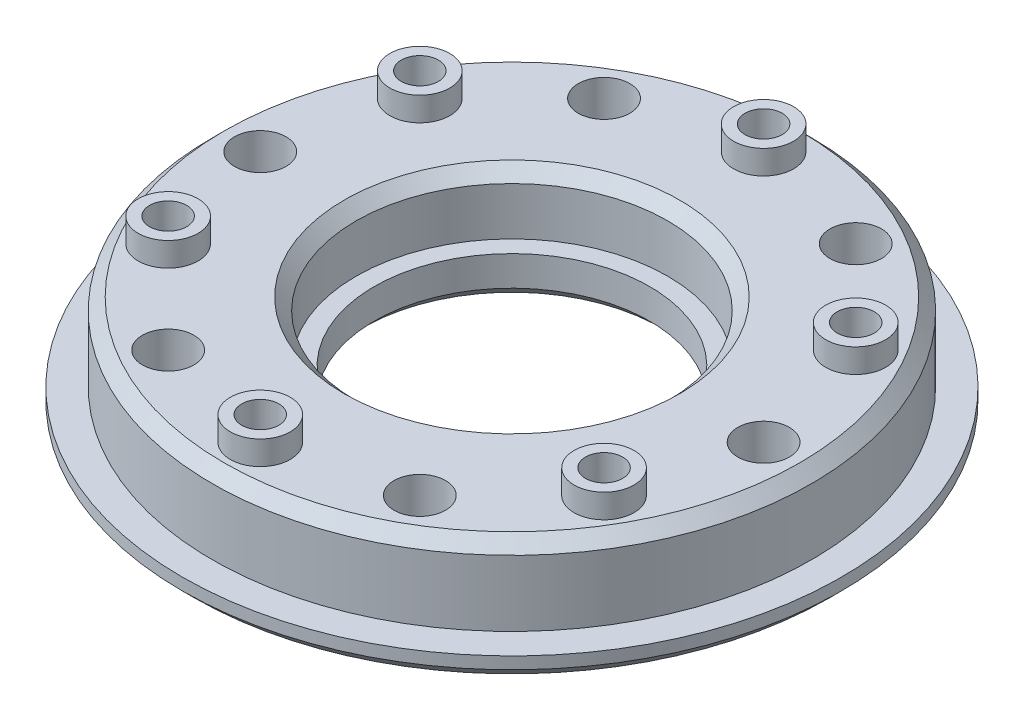
SolidWorks part; units mm, degrees
material "Like ABS"
ref_plane "Front Plane" through (0, 0, 0) normal (0, 0, 1) x (1, 0, 0)
ref_plane "Top Plane" through (0, 0, 0) normal (0, 1, 0) x (1, 0, 0)
ref_plane "Right Plane" through (0, 0, 0) normal (1, 0, 0) x (0, 0, -1)
sketch "Sketch1" plane through (0, 0, 0) normal (0, 1, 0) x (1, 0, 0)
  circle A0 centre (0, 0) radius 27.5
  dimension "D1" = 55
extrude "Boss-Extrude1" add sketch "Sketch1" along normal blind 2
sketch "Sketch2" plane through (0, 2, 0) normal (0, 1, 0) x (1, 0, 0)
  circle A0 centre (0, 0) radius 25
  dimension "D1" = 50
extrude "Boss-Extrude2" add sketch "Sketch2" along normal blind 6.5
sketch "Sketch3" plane through (0, 8.5, 0) normal (0, 1, 0) x (1, 0, 0)
  circle A0 centre (0, 0) radius 13
  dimension "D1" = 26
extrude "Cut-Extrude1" cut sketch "Sketch3" against normal blind 5
sketch "Sketch4" plane through (0, 8.5, 0) normal (0, 1, 0) x (1, 0, 0)
  circle A0 centre (0, 0) radius 11.5
  dimension "D1" = 23
extrude "Cut-Extrude2" cut sketch "Sketch4" against normal up to surface (8.5 mm away) up to face at (0, 0, 27.5)
chamfer "Chamfer1" distance 1 angle 45 4 edges at (0, 0, 27.5) (0, 0, 11.5) (0, 8.5, 13) (0, 8.5, 25)
sketch "Sketch5" plane through (0, 0, 0) normal (0, -1, 0) x (1, 0, 0)
  line L0 (0, 0) -> (0, 21) construction
  circle A0 centre (0, 21) radius 1.55
  dimension "D2" = 3.1
  dimension "D1" = 21
extrude "Cut-Extrude3" cut sketch "Sketch5" against normal up to surface (8.5 mm away) up to face at (0, 8.5, 14)
sketch "Sketch6" plane through (0, 0, 0) normal (0, -1, 0) x (1, 0, 0)
  circle A0 centre (0, 21) radius 3
  dimension "D1" = 6
extrude "Cut-Extrude4" cut sketch "Sketch6" against normal blind 6
chamfer "Chamfer2" distance 1 angle 45 1 edges at (0, 0, 18)
pattern_circular "CirPattern1" count 6 over 360 about axis through (0, 3.5, 0) along (0, 1, 0) of "Cut-Extrude3", "Cut-Extrude4", "Chamfer2" reverse direction yes
sketch "Sketch7" plane through (0, 8.5, 0) normal (0, 1, 0) x (1, 0, 0)
  line L0 (0, 21) -> (0, 0) construction
  line L1 (0, 0) -> (-10.5, 18.1865) construction
  circle A0 centre (-10.5, 18.1865) radius 1.55
  dimension "D3" = 3.1
  dimension "D1" = 30
  dimension "D2" = 21
extrude "Cut-Extrude5" cut sketch "Sketch7" against normal up to surface (8.5 mm away) up to face at (18.1865, 0, 14.5)
sketch "Sketch8" plane through (0, 8.5, 0) normal (0, 1, 0) x (1, 0, 0)
  circle A0 centre (-10.5, 18.1865) radius 2.15
  dimension "D1" = 4.3
extrude "Cut-Extrude6" cut sketch "Sketch8" against normal blind 4.5
pattern_circular "CirPattern2" count 6 over 360 about axis through (0, 3.5, 0) along (0, 1, 0) of "Cut-Extrude6", "Cut-Extrude5"
sketch "Sketch9" plane through (0, 8.5, 0) normal (0, 1, 0) x (1, 0, 0)
  circle A0 centre (0, 21) radius 2.5
  circle A1 centre (0, 21) radius 1.55
  dimension "D1" = 3.1
  dimension "D2" = 5
extrude "Boss-Extrude3" add sketch "Sketch9" along normal blind 2
pattern_circular "CirPattern3" count 6 over 360 about axis through (0, 8.5, 0) along (0, -1, 0) of "Boss-Extrude3"
